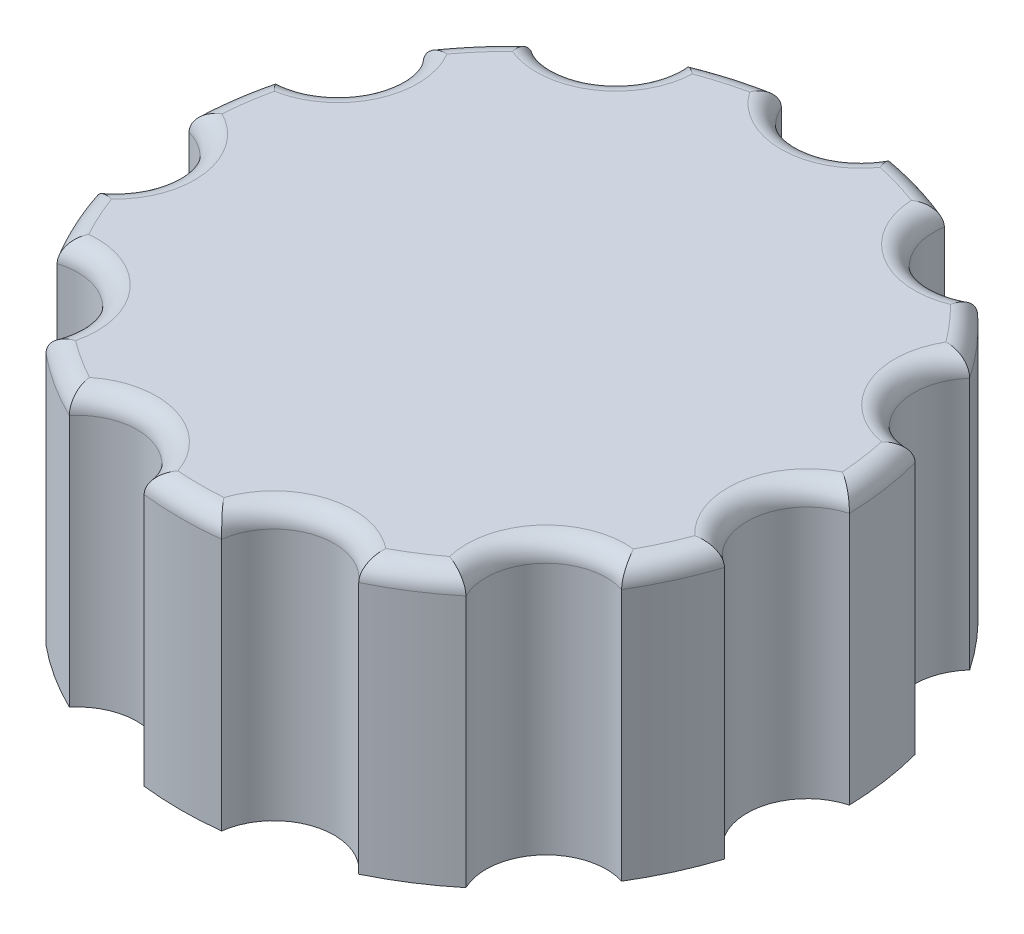
SolidWorks part; units mm, degrees
ref_plane "Front Plane" through (0, 0, 0) normal (0, 0, 1) x (1, 0, 0)
ref_plane "Top Plane" through (0, 0, 0) normal (0, 1, 0) x (1, 0, 0)
ref_plane "Right Plane" through (0, 0, 0) normal (1, 0, 0) x (0, 0, -1)
sketch "Sketch1" plane through (0, 0, 0) normal (0, 1, 0) x (1, 0, 0)
  line L0 (0, 8.5) -> (0, 9) construction
  circle A0 centre (0, 0) radius 3.35
  circle A1 centre (0, 0) radius 8.5
  circle A2 centre (0, 9) radius 1.55
  circle A3 centre (4.8658, 7.5713) radius 1.55
  circle A4 centre (8.1867, 3.7387) radius 1.55
  circle A5 centre (8.9084, -1.2808) radius 1.55
  circle A6 centre (6.8017, -5.8937) radius 1.55
  circle A7 centre (2.5356, -8.6354) radius 1.55
  circle A8 centre (-2.5356, -8.6354) radius 1.55
  circle A9 centre (-6.8017, -5.8937) radius 1.55
  circle A10 centre (-8.9084, -1.2808) radius 1.55
  circle A11 centre (-8.1867, 3.7387) radius 1.55
  circle A12 centre (-4.8658, 7.5713) radius 1.55
  point P8 (-5.8063, 8.009)
  point P9 (0, 0)
  point P31 (0, 0)
  dimension "D1" = 6.7
  dimension "D2" = 17
  dimension "D3" = 3.1
  dimension "D4" = 0.5
  dimension "D5" = 11
extrude "Boss-Extrude1" add sketch "Sketch1" against normal blind 6 contours A1 A12 A11 A10 A9 A8 A7 A6 A5 A4 A3 A2 A0 region at (7.1371, 0, 1.0262)
extrude "Boss-Extrude2" add sketch "Sketch1<2>" along normal blind 1 contours A1 A12 A11 A10 A9 A8 A7 A6 A5 A4 A3 A2 A0 | A0 region at (0, 0, 0) region at (7.1371, 0, 1.0262)
sketch "Sketch1<2>" plane through (0, 0, 0) normal (0, 1, 0) x (1, 0, 0) same geometry as "Sketch1"
fillet "Fillet1" radius 0.5 22 edges at (-2.3947, 1, -8.1557) (0, 1, -7.45) (2.3947, 1, -8.1557) (4.0278, 1, -6.2673) (6.4239, 1, -5.5663) (6.7768, 1, -3.0948) (8.4135, 1, -1.2097) (7.3742, 1, 1.0602) (7.7319, 1, 3.531) (5.6303, 1, 4.8787) (4.5954, 1, 7.1507) (2.0989, 1, 7.1482) (0, 1, 8.5) (-2.0989, 1, 7.1482) (-4.5954, 1, 7.1507) (-5.6303, 1, 4.8787) (-7.7319, 1, 3.531) (-7.3742, 1, 1.0602) (-8.4135, 1, -1.2097) (-6.7768, 1, -3.0948) (-6.4239, 1, -5.5663) (-4.0278, 1, -6.2673)
